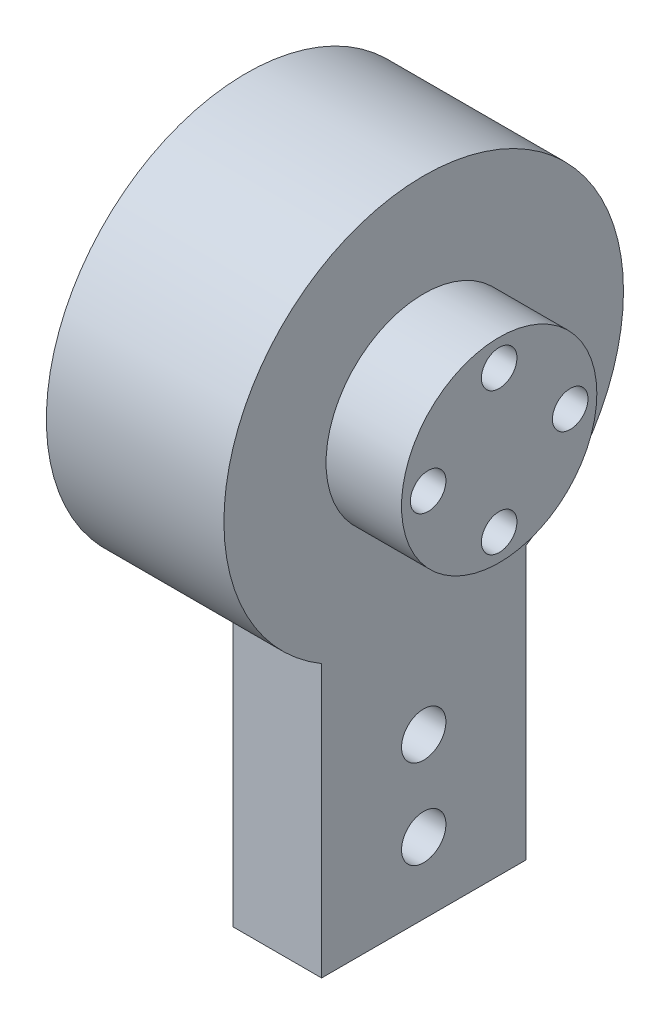
SolidWorks part; units mm, degrees
material "1060 Alloy"
ref_plane "Front Plane" through (0, 0, 0) normal (0, 0, 1) x (1, 0, 0)
ref_plane "Top Plane" through (0, 0, 0) normal (0, 1, 0) x (1, 0, 0)
ref_plane "Right Plane" through (0, 0, 0) normal (1, 0, 0) x (0, 0, -1)
sketch "Sketch2" plane through (0, 0, 0) normal (1, 0, 0) x (0, 0, -1)
  circle A0 centre (0, 0) radius 11
  circle A1 centre (0, 0) radius 19.5
  circle A2 centre (0, 0) radius 22.5
  dimension "D1" = 22
  dimension "D2" = 39
  dimension "D3" = 45
ref_plane "Plane1" through (0, -50, 0) normal (0, 1, 0) x (1, 0, 0)
extrude "Boss-Extrude8" add sketch "Sketch2" against normal blind 20 contours A1 A0 | A2 A1 | A0 region at (0, 0, 18.9485) region at (0, 0, 21.8636)
extrude "Boss-Extrude9" add sketch "Sketch2<10>" along normal blind 8.5 separate body contours A0 region at (0, 0, 0)
sketch "Sketch2<10>" plane through (0, 0, 0) normal (1, 0, 0) x (0, 0, -1) same geometry as "Sketch2"
sketch "Sketch8" plane through (0, -50, 0) normal (0, 1, 0) x (1, 0, 0)
  line L0 (0, -22.5) -> (0, 22.5) construction
  line L2 (-10, 11.5) -> (0, 11.5)
  line L3 (-10, 11.5) -> (-10, -11.5)
  line L4 (-10, -11.5) -> (0, -11.5)
  line L5 (0, 11.5) -> (0, -11.5)
  line L6 (-10, 11.5) -> (0, -11.5) construction
  line L7 (-10, -11.5) -> (0, 11.5) construction
  point P1 (-5, 0)
  dimension "D1" = 10
  dimension "D2" = 23
extrude "Boss-Extrude10" add sketch "Sketch8" along normal up to next
sketch "Sketch9" plane through (0, 0, 0) normal (1, 0, 0) x (0, 0, -1)
  line L0 (15.675, -50) -> (-15.675, -50) construction
  line L1 (-11.5, -19.3391) -> (-11.5, -50) construction
  circle A0 centre (0, -42) radius 2.5
  circle A1 centre (0, -32) radius 2.5
  dimension "D3" = 5
  dimension "D4" = 5
  dimension "D1" = 8
  dimension "D2" = 10
  dimension "D5" = 11.5
extrude "Cut-Extrude3" cut sketch "Sketch9" against normal through all
sketch "Sketch10" plane through (-20, 0, 0) normal (-1, 0, 0) x (0, 0, 1)
  circle A0 centre (0, 0) radius 4
  dimension "D1" = 8
extrude "Cut-Extrude4" cut sketch "Sketch10" against normal blind 20
sketch "Sketch11" plane through (8.5, 0, 0) normal (1, 0, 0) x (0, 0, -1)
  circle A0 centre (0, 8) radius 2
  circle A1 centre (8, 0) radius 2
  circle A2 centre (0, -8) radius 2
  circle A3 centre (-8, 0) radius 2
  dimension "D1" = 4
  dimension "D2" = 8
  dimension "D3" = 4
extrude "Cut-Extrude7" cut sketch "Sketch11" against normal through all
